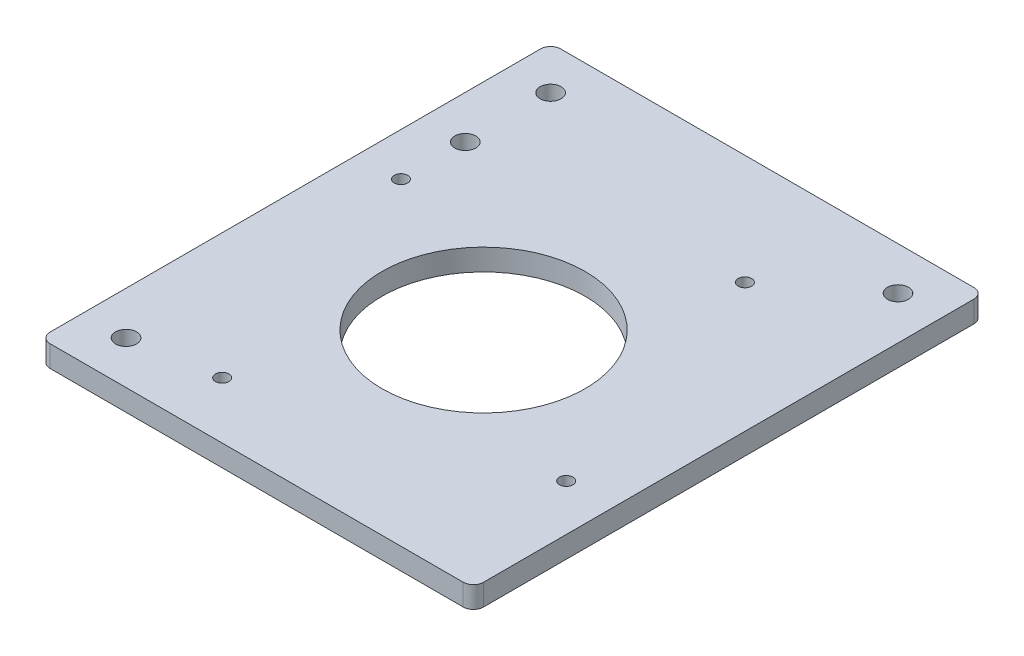
SolidWorks part; units mm, degrees
ref_plane "Front Plane" through (0, 0, 0) normal (0, 0, 1) x (1, 0, 0)
ref_plane "Top Plane" through (0, 0, 0) normal (0, 1, 0) x (1, 0, 0)
ref_plane "Right Plane" through (0, 0, 0) normal (1, 0, 0) x (0, 0, -1)
sketch "Sketch1" plane through (0, 0, 0) normal (0, 1, 0) x (1, 0, 0)
  line L0 (0.7175, -80.6209) -> (93.6586, -80.6209) construction
  line L1 (5.6586, 35.1791) -> (133.6586, 35.1791)
  line L3 (5.6586, -115.6209) -> (133.6586, -115.6209)
  line L4 (133.6586, 35.1791) -> (133.6586, -115.6209)
  line L5 (-22.3414, -80.6209) -> (93.6586, -80.6209) construction
  line L6 (93.6586, -80.6209) -> (101.6586, -72.6209) construction
  line L7 (101.6586, -72.6209) -> (101.6586, -23.6209) construction
  line L12 (101.6586, -23.6209) -> (93.6586, -15.6209) construction
  line L13 (93.6586, -15.6209) -> (0.7175, -15.6209) construction
  line L14 (93.6586, -15.6209) -> (-22.3414, -15.6209) construction
  line L16 (18.3586, 22.4791) -> (5.6586, 22.4791) construction
  line L17 (18.3586, 22.4791) -> (18.3586, 35.1791) construction
  line L18 (120.9586, 22.4791) -> (120.9586, 35.1791) construction
  line L19 (120.9586, 22.4791) -> (133.6586, 22.4791) construction
  line L20 (18.3586, -102.9209) -> (5.6586, -102.9209) construction
  line L21 (18.3586, -102.9209) -> (18.3586, -99.8209) construction
  line L22 (18.3586, -102.9209) -> (18.3586, -115.6209) construction
  line L23 (18.3586, 22.4791) -> (21.4586, 22.4791) construction
  line L24 (5.6586, -26.1209) -> (21.8586, -26.1209) construction
  line L25 (120.9586, 22.4791) -> (120.9586, 19.3791) construction
  line L30 (5.6586, 35.1791) -> (5.6586, -115.6209)
  line L31 (21.8586, -26.1209) -> (-20.3414, -26.1209) construction
  line L32 (18.3586, 22.4791) -> (18.3586, -2.7209) construction
  line L35 (-20.3414, -30.1209) -> (21.8586, -30.1209) construction
  line L36 (5.6586, -30.1209) -> (21.8586, -30.1209) construction
  line L37 (18.3586, -2.7209) -> (21.4586, -2.7209) construction
  circle A0 centre (69.1586, -48.1209) radius 30
  circle A1 centre (18.3586, 22.4791) radius 3.1
  circle A2 centre (120.9586, 22.4791) radius 3.1
  circle A4 centre (18.3586, -102.9209) radius 3.1
  arc A5 (21.8586, -30.1209) -> (21.8586, -26.1209) centre (21.8586, -28.1209) ccw construction
  circle A6 centre (18.3586, -2.7209) radius 3.1
  dimension "D4" = 60
  dimension "D5" = 88
  dimension "D6" = 6.2
  dimension "D1" = 50.8
  dimension "D2" = 35
  dimension "D3" = 32
  dimension "D7" = 12.7
  dimension "D8" = 25.2
extrude "Boss-Extrude1" add sketch "Sketch1" along normal blind 6.35
fillet "Fillet1" radius 3 4 edges at (133.6586, 3.175, -35.1791) (133.6586, 3.175, 115.6209) (5.6586, 3.175, 115.6209) (5.6586, 3.175, -35.1791)
sketch "Sketch3" plane through (0, 6.35, 0) normal (0, 1, 0) x (1, 0, 0)
  line L0 (18.3586, 22.4791) -> (18.3586, -102.9209) construction
  line L1 (18.3586, -21.7273) -> (95.5522, 2.6791) construction
  line L2 (18.3586, -21.7273) -> (42.765, -98.9209) construction
  line L3 (42.765, -98.9209) -> (119.9586, -74.5145) construction
  line L4 (95.5522, 2.6791) -> (119.9586, -74.5145) construction
  line L5 (18.3586, -21.7273) -> (119.9586, -74.5145) construction
  line L6 (42.765, -98.9209) -> (95.5522, 2.6791) construction
  line L7 (5.4076, -14.9985) -> (102.2809, 15.6301) construction
  line L8 (5.4076, -14.9985) -> (36.0362, -111.8719) construction
  line L9 (36.0362, -111.8719) -> (132.9096, -81.2433) construction
  line L10 (102.2809, 15.6301) -> (132.9096, -81.2433) construction
  circle A0 centre (18.3586, -21.7273) radius 1.985
  circle A1 centre (69.1586, -48.1209) radius 30 construction
  circle A2 centre (95.5522, 2.6791) radius 1.985
  circle A3 centre (119.9586, -74.5145) radius 1.985
  circle A4 centre (42.765, -98.9209) radius 1.985
  point P4 (69.1586, -48.1209)
  point P23 (69.1586, -48.1209)
  dimension "D5" = 3.97
  dimension "D1" = 80.96
  dimension "D2" = 101.6
  dimension "D3" = 90
  dimension "D4" = 90
  dimension "D6" = 4
extrude "Cut-Extrude1" cut sketch "Sketch3" against normal through all
